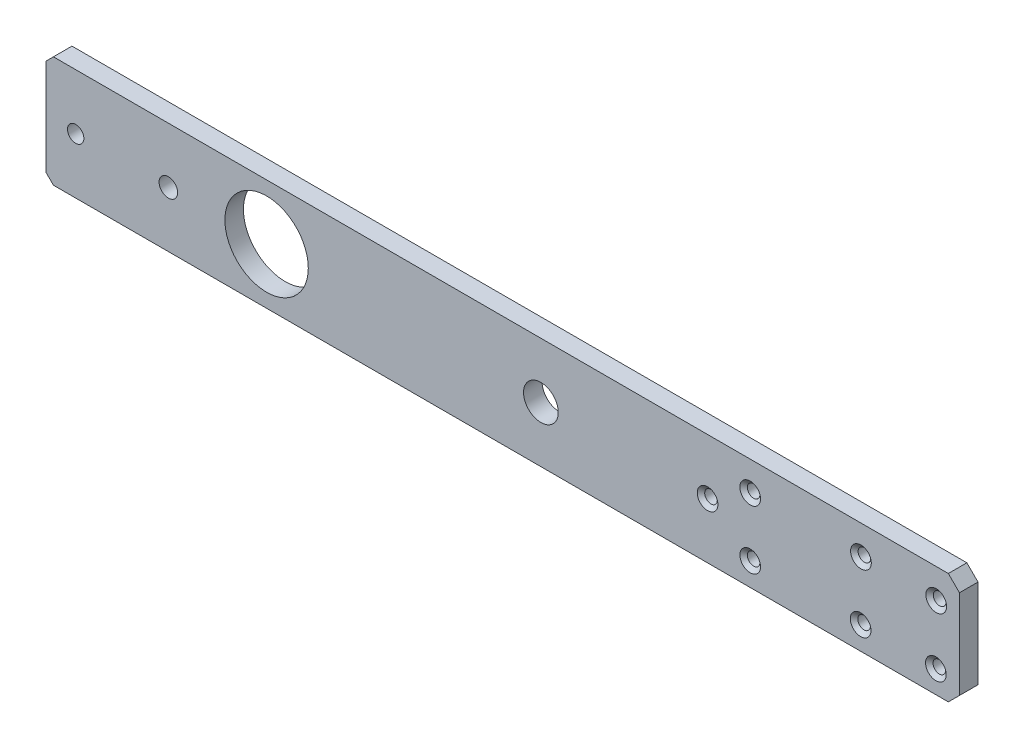
SolidWorks part; units mm, degrees
material "6061-T6 (SS)"
ref_plane "Front Plane" through (0, 0, 0) normal (0, 0, 1) x (1, 0, 0)
ref_plane "Top Plane" through (0, 0, 0) normal (0, 1, 0) x (1, 0, 0)
ref_plane "Right Plane" through (0, 0, 0) normal (1, 0, 0) x (0, 0, -1)
sketch "Sketch1" plane through (0, 0, 0) normal (0, 0, 1) x (1, 0, 0)
  line L0 (0, 19.05) -> (-28.575, 19.05)
  line L1 (0, -19.05) -> (247.2819, -19.05)
  line L2 (0, -19.05) -> (0, 19.05) construction
  line L3 (0, 19.05) -> (254, 19.05)
  line L5 (-28.575, 19.05) -> (-28.575, -19.05)
  line L6 (-28.575, -19.05) -> (0, -19.05)
  line L8 (254, 19.05) -> (247.2819, -19.05)
  circle A1 centre (0, 0) radius 14.2875
  dimension "D3" = 28.575
  dimension "D1" = 38.1
  dimension "D2" = 254
  dimension "D4" = 80
extrude "Boss-Extrude1" add sketch "Sketch1" along normal mid plane 6.35
hole_wizard "#6 Clearance Hole3" positions "Sketch8" profile "Sketch7" hole size "#6" standard "ANSI Inch" end condition through all
sketch "Sketch8" plane through (0, 0, 3.175) normal (0, 0, 1) x (1, 0, 0)
  point P0 (229.3887, 8.9238)
  point P3 (229.2824, -11.3468)
  point P6 (203.5032, -11.1439)
  point P9 (203.6088, 8.9914)
  point P12 (165.6722, 8.9914)
  point P15 (165.6722, -11.1439)
  point P18 (151.0672, 0)
sketch "Sketch7" plane through (229.3887, 8.9238, 3.175) normal (1, 0, 0) x (0, -1, 0)
  line L0 (0, 0) -> (0, 6.35)
  line L1 (0, 6.35) -> (2.1526, 6.35)
  line L2 (2.1526, 6.35) -> (2.1526, 0)
  line L5 (2.1526, 0) -> (0, 0)
  line L11 (0, -6.35) -> (0, 107.95) construction
  dimension "Thru Hole Dia." = 4.3053
  dimension "Thru Hole Depth" = 6.35
sketch "Sketch9" plane through (0, 0, 3.175) normal (0, 0, 1) x (1, 0, 0)
  line L0 (254, 19.05) -> (247.2819, -19.05)
  line L1 (254, 19.05) -> (237.3521, 19.05)
  line L2 (254, 19.05) -> (-28.575, 19.05) construction
  line L3 (237.3521, 19.05) -> (237.3521, -19.05)
  line L4 (-28.575, -19.05) -> (247.2819, -19.05) construction
  line L5 (237.3521, -19.05) -> (247.2819, -19.05)
  line L6 (243.8073, 17.5595) -> (237.0893, -20.5405) construction
extrude "Cut-Extrude1" cut sketch "Sketch9" against normal through all
chamfer "Chamfer1" distance 3.81 angle 45 4 edges at (-28.575, -19.05, 0) (-28.575, 19.05, 0) (237.3521, 19.05, 0) (237.3521, -19.05, 0)
hole_wizard "CSK for #6 Flat Head Machine Screw (100)2" positions "Sketch12" profile "Sketch13" countersink size "#6" standard "ANSI Inch" end condition through all
sketch "Sketch12" plane through (0, 0, 3.175) normal (0, 0, 1) x (1, 0, 0)
  point P0 (203.6088, 8.9914)
  point P3 (203.5032, -11.1439)
  point P6 (229.2824, -11.3468)
  point P9 (229.3887, 8.9238)
  point P12 (165.6722, 8.9914)
  point P15 (165.6722, -11.1439)
  point P18 (151.0672, 0)
sketch "Sketch13" plane through (203.6088, 8.9914, 3.175) normal (1, 0, 0) x (0, -1, 0)
  line L0 (0, 0) -> (0, 6.35)
  line L1 (0, 6.35) -> (2.1526, 6.35)
  line L2 (2.1526, 6.35) -> (2.1526, 1.1669)
  line L3 (2.1526, 1.1669) -> (3.5433, 0)
  line L5 (3.5433, 0) -> (0, 0)
  line L6 (-2.1526, 1.1669) -> (-3.5433, 0) construction
  line L11 (0, -6.35) -> (0, 107.95) construction
  dimension "Thru Hole Dia." = 4.3053
  dimension "Thru Hole Depth" = 6.35
  dimension "Near C'Sink Dia." = 7.0866
  dimension "Near C'Sink Angle" = 100
sketch "Sketch14" plane through (0, 0, 3.175) normal (0, 0, 1) x (1, 0, 0)
  line L1 (-24.765, 19.05) -> (-75.565, 19.05)
  line L2 (-24.765, 19.05) -> (-24.765, -19.05)
  line L3 (-24.765, -19.05) -> (-75.565, -19.05)
  line L4 (-75.565, 19.05) -> (-75.565, -19.05)
  dimension "D1" = 50.8
extrude "Boss-Extrude2" add sketch "Sketch14" against normal through all
chamfer "Chamfer2" distance 2.54 angle 45 2 edges at (-75.565, 19.05, 0) (-75.565, -19.05, 0)
hole_wizard "CSK for #10 Flat Head Machine Screw (100)1" positions "Sketch15" profile "Sketch16" countersink size "#10" standard "ANSI Inch" end condition through all
sketch "Sketch15" plane through (0, 0, -3.175) normal (0, 0, 1) x (1, 0, 0)
  line L0 (0, 0) -> (-75.565, 0) construction
  line L1 (-75.565, 16.51) -> (-75.565, -16.51) construction
  point P0 (-65.405, 0)
  dimension "D1" = 10.16
sketch "Sketch16" plane through (-65.405, 0, -3.175) normal (1, 0, 0) x (0, 1, 0)
  line L0 (0, 0) -> (0, 6.35)
  line L1 (0, 6.35) -> (2.8067, 6.35)
  line L2 (2.8067, 6.35) -> (2.8067, 1.7477)
  line L3 (2.8067, 1.7477) -> (4.8895, 0)
  line L5 (4.8895, 0) -> (0, 0)
  line L6 (-2.8067, 1.7477) -> (-4.8895, 0) construction
  line L11 (0, -6.35) -> (0, 107.95) construction
  dimension "Thru Hole Dia." = 5.6134
  dimension "Thru Hole Depth" = 6.35
  dimension "Near C'Sink Dia." = 9.779
  dimension "Near C'Sink Angle" = 100
hole_wizard "1/4 (0.25) Diameter Hole1" positions "Sketch19" profile "Sketch20" hole size "1/4" standard "ANSI Inch" end condition through all
sketch "Sketch19" plane through (0, 0, -3.175) normal (0, 0, -1) x (-1, 0, 0)
  line L0 (75.565, 0) -> (33.655, 0) construction
  line L1 (75.565, 16.51) -> (75.565, -16.51) construction
  circle A1 centre (65.405, 0) radius 4.8895 construction
  point P0 (33.655, 0)
  dimension "D1" = 31.75
sketch "Sketch20" plane through (-33.655, 0, -3.175) normal (1, 0, 0) x (0, 1, 0)
  line L0 (0, 0) -> (0, 6.35)
  line L1 (0, 6.35) -> (3.175, 6.35)
  line L2 (3.175, 6.35) -> (3.175, 0)
  line L5 (3.175, 0) -> (0, 0)
  line L11 (0, -6.35) -> (0, 107.95) construction
  dimension "Thru Hole Dia." = 6.35
  dimension "Thru Hole Depth" = 6.35
hole_wizard "15/32 (0.46875) Diameter Hole1" positions "Sketch21" profile "Sketch22" hole size "15/32" standard "ANSI Inch" end condition through all
sketch "Sketch21" plane through (0, 0, -3.175) normal (0, 0, -1) x (-1, 0, 0)
  line L0 (75.565, 16.51) -> (75.565, -16.51) construction
  point P0 (-93.9672, 0)
  dimension "D1" = 169.5322
sketch "Sketch22" plane through (93.9672, 0, -3.175) normal (1, 0, 0) x (0, 1, 0)
  line L0 (0, 0) -> (0, 6.35)
  line L1 (0, 6.35) -> (5.9531, 6.35)
  line L2 (5.9531, 6.35) -> (5.9531, 0)
  line L5 (5.9531, 0) -> (0, 0)
  line L11 (0, -6.35) -> (0, 107.95) construction
  dimension "Thru Hole Dia." = 11.9062
  dimension "Thru Hole Depth" = 6.35
